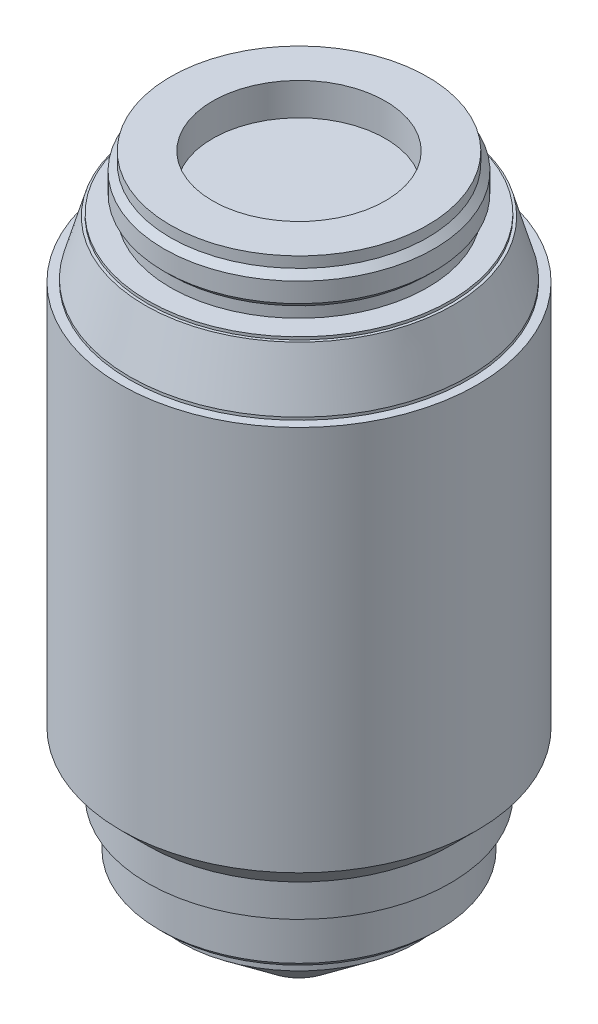
SolidWorks part; units mm, degrees
ref_plane "Front Plane" through (0, 0, 0) normal (0, 0, 1) x (1, 0, 0)
ref_plane "Top Plane" through (0, 0, 0) normal (0, 1, 0) x (1, 0, 0)
ref_plane "Right Plane" through (0, 0, 0) normal (1, 0, 0) x (0, 0, -1)
sketch "Sketch1" plane through (0, 0, 0) normal (1, 0, 0) x (0, 0, -1)
  line L0 (0, 40) -> (0, -40) construction
  line L1 (0, 32) -> (0, -32)
  line L2 (0, -32) -> (-3.25, -32)
  line L3 (-3.25, -32) -> (-10.9, -26.0232)
  line L4 (-10.9, -26.0232) -> (-10.9, -24.5)
  line L5 (-10.9, -24.5) -> (-12.4, -24.5)
  line L6 (-12.4, -24.5) -> (-12.9, -24)
  line L7 (-12.9, -24) -> (-12.9, -19.7)
  line L8 (-12.9, -19.7) -> (-14, -19.7)
  line L9 (-14, -19.7) -> (-14, -16.7)
  line L10 (-14, -16.7) -> (-16.5, -14.2)
  line L11 (-16.5, -14.2) -> (-16.5, 21.5)
  line L12 (-16.5, 21.5) -> (-15.6837, 21.5)
  line L13 (-15.6837, 21.5) -> (-15.6837, 21.75)
  line L14 (-15.6837, 21.75) -> (-14.25, 26.75)
  line L15 (-14.25, 26.75) -> (-14, 26.75)
  line L16 (-14, 26.75) -> (-14, 27)
  line L17 (-14, 27) -> (-11.9, 27)
  line L18 (-11.9, 27) -> (-11.9, 28)
  line L19 (-11.9, 28) -> (-12.5, 28.6)
  line L20 (-12.5, 28.6) -> (-12.5, 30.4)
  line L21 (-12.5, 30.4) -> (-11.9, 31)
  line L22 (-11.9, 31) -> (-11.9, 32)
  line L23 (-11.9, 32) -> (0, 32)
  point P2 (0, 0)
  point P6 (0, 0)
  point P38 (-12.5, 29.5)
  point P57 (-14, -18.2)
  dimension "D1" = 80
  dimension "D2" = 64
  dimension "D3" = 6.5
  dimension "D4" = 21.8
  dimension "D5" = 5
  dimension "D6" = 23.8
  dimension "D7" = 1
  dimension "D8" = 1
  dimension "D9" = 25
  dimension "D10" = 45
  dimension "D11" = 0.25
  dimension "D12" = 28.5
  dimension "D13" = 33
  dimension "D14" = 74
  dimension "D15" = 0.25
  dimension "D16" = 38
  dimension "D17" = 25.8
  dimension "D18" = 5.5
  dimension "D19" = 0.25
  dimension "D20" = 38.2
  dimension "D21" = 28
  dimension "D22" = 45
  dimension "D23" = 41.2
  dimension "D24" = 51.5
  dimension "D25" = 45
  dimension "D26" = 0.5
revolve "Revolve1" add sketch "Sketch1" angle 360 about L0
cosmetic thread "Cosmetic Thread1" parameters "D2"=25
sketch "Sketch2" plane through (0, 32, 0) normal (0, 1, 0) x (1, 0, 0)
  circle A0 centre (0, 0) radius 8
  dimension "D1" = 16
extrude "Cut-Extrude1" cut sketch "Sketch2" against normal blind 3
sketch "Sketch3" plane through (0, -32, 0) normal (0, -1, 0) x (-1, 0, 0)
  circle A0 centre (0, 0) radius 2.5
  dimension "D1" = 5
extrude "Cut-Extrude2" cut sketch "Sketch3" against normal blind 0.01
ref_plane "WD" through (0, -32.8, 0) normal (0, -1, 0) x (-1, 0, 0)
ref_plane "coverslip" through (0, -32.97, 0) normal (0, -1, 0) x (-1, 0, 0)
ref_axis "Axis1" through (0, -32.97, -3.575) along (0, 0, 1)
ref_axis "Axis2" through (-3.6995, -32.97, 0) along (1, 0, 0)
sketch "Sketch4" plane through (0, -32.97, 0) normal (0, -1, 0) x (-1, 0, 0)
  line L1 (-0.128, 0.625) -> (0.128, 0.625) construction
  line L2 (-0.128, 0.625) -> (-0.128, -0.625) construction
  line L3 (-0.128, -0.625) -> (0.128, -0.625) construction
  line L4 (0.128, 0.625) -> (0.128, -0.625) construction
  line L5 (-0.128, 0.625) -> (0.128, -0.625) construction
  line L6 (-0.128, -0.625) -> (0.128, 0.625) construction
  point P0 (0, 0)
  dimension "D1" = 1.25
  dimension "D2" = 0.256
ref_axis "Axis3" through (-0.128, -32.97, -0.625) along (0, 0, 1)
ref_axis "Axis4" through (0.128, -32.97, -0.625) along (0, 0, 1)
